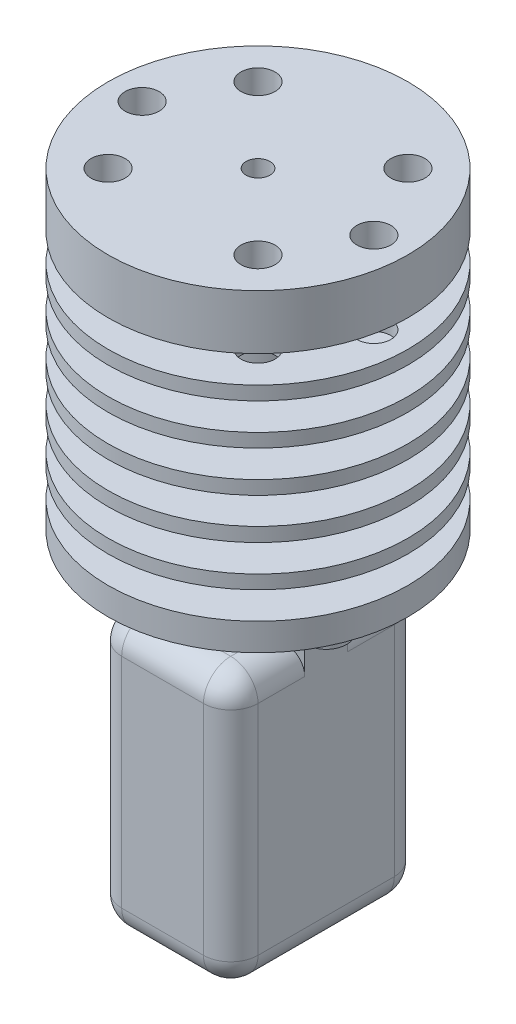
SolidWorks part; units mm, degrees
ref_plane "Front Plane" through (0, 0, 0) normal (0, 0, 1) x (1, 0, 0)
ref_plane "Top Plane" through (0, 0, 0) normal (0, 1, 0) x (1, 0, 0)
ref_plane "Right Plane" through (0, 0, 0) normal (1, 0, 0) x (0, 0, -1)
sketch "Sketch1" plane through (0, 0, 0) normal (0, 1, 0) x (1, 0, 0)
  circle A0 centre (0, 0) radius 11
  dimension "D1" = 22
extrude "Boss-Extrude2" add sketch "Sketch1" against normal blind 4
sketch "Sketch2" plane through (0, -4, 0) normal (0, -1, 0) x (-1, 0, 0)
  circle A0 centre (0, 0) radius 5
  dimension "D1" = 10
extrude "Boss-Extrude3" add sketch "Sketch2" along normal blind 2
sketch "Sketch3" plane through (0, -6, 0) normal (0, -1, 0) x (1, 0, 0)
  circle A0 centre (0, 0) radius 11
extrude "Boss-Extrude4" add sketch "Sketch3" along normal blind 1.0022
sketch "Sketch4" plane through (0, -7.0022, 0) normal (0, -1, 0) x (-1, 0, 0)
  circle A0 centre (0, 0) radius 5
extrude "Boss-Extrude5" add sketch "Sketch4" along normal blind 2
sketch "Sketch5" plane through (0, -9.0022, 0) normal (0, -1, 0) x (1, 0, 0)
  circle A0 centre (0, 0) radius 11
extrude "Boss-Extrude6" add sketch "Sketch5" along normal blind 1 contours A0
sketch "Sketch6" plane through (0, -10.0022, 0) normal (0, -1, 0) x (-1, 0, 0)
  circle A0 centre (0, 0) radius 5
extrude "Boss-Extrude7" add sketch "Sketch6" along normal blind 2
sketch "Sketch7" plane through (0, -12.0022, 0) normal (0, -1, 0) x (-1, 0, 0)
  circle A0 centre (0, 0) radius 11
extrude "Boss-Extrude8" add sketch "Sketch7" along normal blind 1
sketch "Sketch8" plane through (0, -13.0022, 0) normal (0, -1, 0) x (-1, 0, 0)
  circle A0 centre (0, 0) radius 5
extrude "Boss-Extrude9" add sketch "Sketch8" along normal blind 2
sketch "Sketch9" plane through (0, -15.0022, 0) normal (0, -1, 0) x (-1, 0, 0)
  circle A0 centre (0, 0) radius 11
extrude "Boss-Extrude10" add sketch "Sketch9" along normal blind 1 and the other way blind 0.0288
sketch "Sketch10" plane through (0, -16.0022, 0) normal (0, -1, 0) x (-1, 0, 0)
  circle A0 centre (0, 0) radius 5
extrude "Boss-Extrude11" add sketch "Sketch10" along normal blind 2
sketch "Sketch11" plane through (0, -18.0022, 0) normal (0, -1, 0) x (-1, 0, 0)
  circle A0 centre (0, 0) radius 11
extrude "Boss-Extrude12" add sketch "Sketch11" along normal blind 1
sketch "Sketch12" plane through (0, -19.0022, 0) normal (0, -1, 0) x (-1, 0, 0)
  circle A0 centre (0, 0) radius 5
extrude "Boss-Extrude13" add sketch "Sketch12" along normal blind 2
sketch "Sketch13" plane through (0, -21.0022, 0) normal (0, -1, 0) x (-1, 0, 0)
  circle A0 centre (0, 0) radius 11
extrude "Boss-Extrude14" add sketch "Sketch13" along normal blind 2
sketch "Sketch14" plane through (0, -23.0022, 0) normal (0, -1, 0) x (-1, 0, 0)
  line L0 (5.45, -1.4309) -> (0.9, -2.8618)
  line L1 (-0.9, -2.8618) -> (-5.45, -1.4309)
  line L2 (-0.9, 2.8618) -> (-5.45, 1.4309)
  line L3 (5.45, 1.4309) -> (0.9, 2.8618)
  arc A0 (5.45, -1.4309) -> (5.45, 1.4309) centre (5, 0) ccw
  arc A1 (-5.45, 1.4309) -> (-5.45, -1.4309) centre (-5, 0) ccw
  arc A2 (0.9, 2.8618) -> (-0.9, 2.8618) centre (0, 0) ccw
  arc A3 (-0.9, -2.8618) -> (0.9, -2.8618) centre (0, 0) ccw
  dimension "D1" = 6
  dimension "D2" = 3
  dimension "D3" = 10
  dimension "D4" = 5
extrude "Boss-Extrude15" add sketch "Sketch14" along normal blind 4
sketch "Sketch15" plane through (0, -27.0022, 0) normal (0, -1, 0) x (-1, 0, 0)
  line L1 (5, -7) -> (-5, -7)
  line L2 (5, -7) -> (5, 7)
  line L3 (5, 7) -> (-5, 7)
  line L4 (-5, -7) -> (-5, 7)
  line L5 (5, -7) -> (-5, 7) construction
  line L6 (5, 7) -> (-5, -7) construction
  point P0 (0, 0)
  dimension "D1" = 10
  dimension "D2" = 14
extrude "Boss-Extrude16" add sketch "Sketch15" along normal blind 20
sketch "Sketch17" plane through (0, -47.0022, 0) normal (0, -1, 0) x (-1, 0, 0)
  circle A0 centre (0, 0) radius 2.5
extrude "Boss-Extrude17" add sketch "Sketch17" along normal blind 3 draft 32
sketch "Sketch18" plane through (0, 0, 0) normal (0, 1, 0) x (1, 0, 0)
  circle A0 centre (0, 0) radius 0.875
extrude "Cut-Extrude2" cut sketch "Sketch18" against normal blind 48 contours A0
sketch "Sketch19" plane through (0, -50.0022, 0) normal (0, -1, 0) x (-1, 0, 0)
  circle A0 centre (0, 0) radius 0.2
extrude "Cut-Extrude3" cut sketch "Sketch19" against normal blind 5
fillet "Fillet1" radius 2 13 edges at (0, -47.0022, 7) (5, -27.0022, -4.2862) (0, -27.0022, 7) (-5, -27.0022, 4.2862) (-5, -27.0022, -4.2862) (-5, -47.0022, 0) (-5, -37.0022, -7) (0, -27.0022, -7) (0, -47.0022, -7) (5, -47.0022, 0) (5, -27.0022, 4.2862) (5, -37.0022, 7) (5, -37.0022, -7)
fillet "Fillet2" radius 2 3 edges at (-4.4142, -46.4164, 6.4142) (-4.4142, -27.588, 6.4142) (-5, -37.0022, 7)
sketch "Sketch20" plane through (0, 0, 0) normal (0, 1, 0) x (1, 0, 0)
  circle A0 centre (-5.5, 5.5) radius 1.25
  circle A1 centre (5.5, 5.5) radius 1.25
  circle A2 centre (-5.5, -5.5) radius 1.25
  circle A3 centre (5.5, -5.5) radius 1.25
  point P8 (4.3936, 3.9995)
  point P9 (3.9601, -3.9601)
  point P10 (5.0043, 4.7482)
  point P11 (5.0043, -6.1273)
  point P12 (-5.9957, -6.1273)
  point P14 (5.0043, -5.5)
  point P15 (5.0043, -5.5)
  point P16 (4.9058, -5.6545)
  point P17 (5.5, 5.5)
  point P18 (-5.5, 5.5)
  point P19 (-5.9957, -5.5)
  dimension "D1" = 2.5
  dimension "D2" = 11
  dimension "D3" = 11
  dimension "D4" = 5.5
  dimension "D5" = 5.5
  dimension "D6" = 5.5
  dimension "D7" = 11
  dimension "D8" = 5.5
  dimension "D9" = 11
extrude "Cut-Extrude4" cut sketch "Sketch20" against normal blind 8
sketch "Sketch22" plane through (0, 0, 0) normal (0, 1, 0) x (1, 0, 0)
  circle A0 centre (-8.5, 0) radius 1.25
  circle A1 centre (8.5, 0) radius 1.25
  dimension "D1" = 2.5
  dimension "D2" = 17
  dimension "D3" = 8.5
extrude "Cut-Extrude5" cut sketch "Sketch22" against normal blind 8
